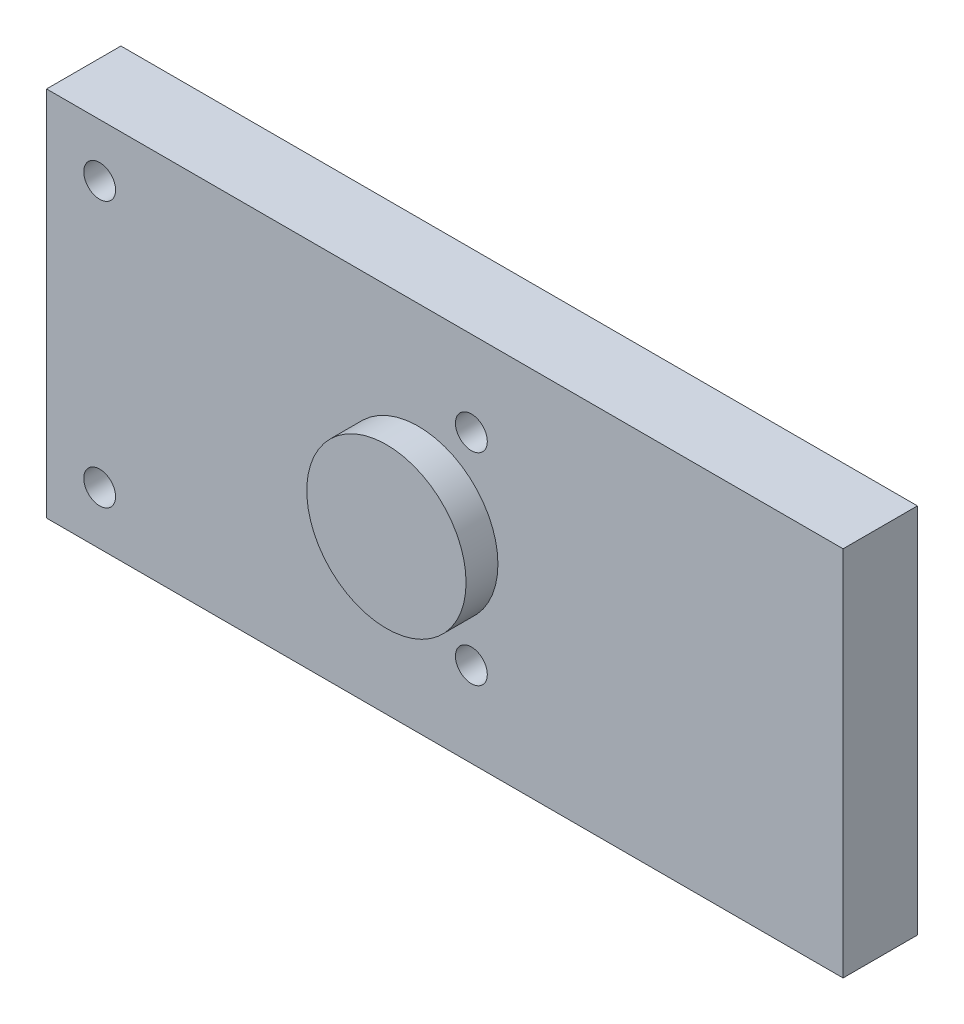
SolidWorks part; units mm, degrees
ref_plane "Front Plane" through (0, 0, 0) normal (0, 0, 1) x (1, 0, 0)
ref_plane "Top Plane" through (0, 0, 0) normal (0, 1, 0) x (1, 0, 0)
ref_plane "Right Plane" through (0, 0, 0) normal (1, 0, 0) x (0, 0, -1)
sketch "Sketch1" plane through (0, 0, 0) normal (0, 0, 1) x (1, 0, 0)
  line L1 (-92.5, 17.5) -> (-17.5, 17.5)
  line L2 (-92.5, 17.5) -> (-92.5, -17.5)
  line L3 (-92.5, -17.5) -> (-17.5, -17.5)
  line L4 (-17.5, 17.5) -> (-17.5, -17.5)
  line L5 (-92.5, 0) -> (-56.7435, 0) construction
  circle A0 centre (-87.5, 12.5) radius 1.5
  circle A1 centre (-87.5, -12.5) radius 1.5
  circle A2 centre (-52.5, 9.5) radius 1.5
  circle A3 centre (-52.5, -9.5) radius 1.5
  circle A4 centre (-57.5, 0) radius 4
  dimension "D2" = 3
  dimension "D5" = 8
  dimension "D6" = 30
  dimension "D7" = 35
  dimension "D1" = 75
  dimension "D3" = 5
  dimension "D4" = 5
extrude "Boss-Extrude1" add sketch "Sketch1" along normal blind 7 contours L4 L1 L2 A4 L3 A3 A2 A0 A1 | L5 A4 | A4 L5 region at (-55, 16.6724, 0) region at (-57.5, 0, 0)
sketch "Sketch2" plane through (-17.5, 0, 0) normal (1, 0, 0) x (0, 0, -1)
  line L1 (0, 25) -> (-7, 25)
  line L2 (0, 25) -> (0, -25)
  line L3 (0, -25) -> (-7, -25)
  line L4 (-7, 25) -> (-7, -25)
  line L6 (-7, 17.5) -> (0, 17.5) construction
  line L7 (-7, -17.5) -> (0, -17.5) construction
  line L8 (-7, 17.5) -> (-7, -17.5) construction
  dimension "D2" = 7.5
  dimension "D3" = 7.5
sketch "Sketch5" plane through (0, 0, 7) normal (0, 0, 1) x (1, 0, 0)
  circle A0 centre (-57.5, 0) radius 7.5
  dimension "D1" = 15
extrude "Boss-Extrude5" add sketch "Sketch5" along normal blind 3
extrude "Cut-Extrude1" cut sketch "Sketch1<3>" along normal blind 3 and the other way blind 3 contours L5 A4 | A4 L5 region at (-57.5, 0, 0)
sketch "Sketch1<3>" plane through (0, 0, 0) normal (0, 0, 1) x (1, 0, 0) same geometry as "Sketch1"
